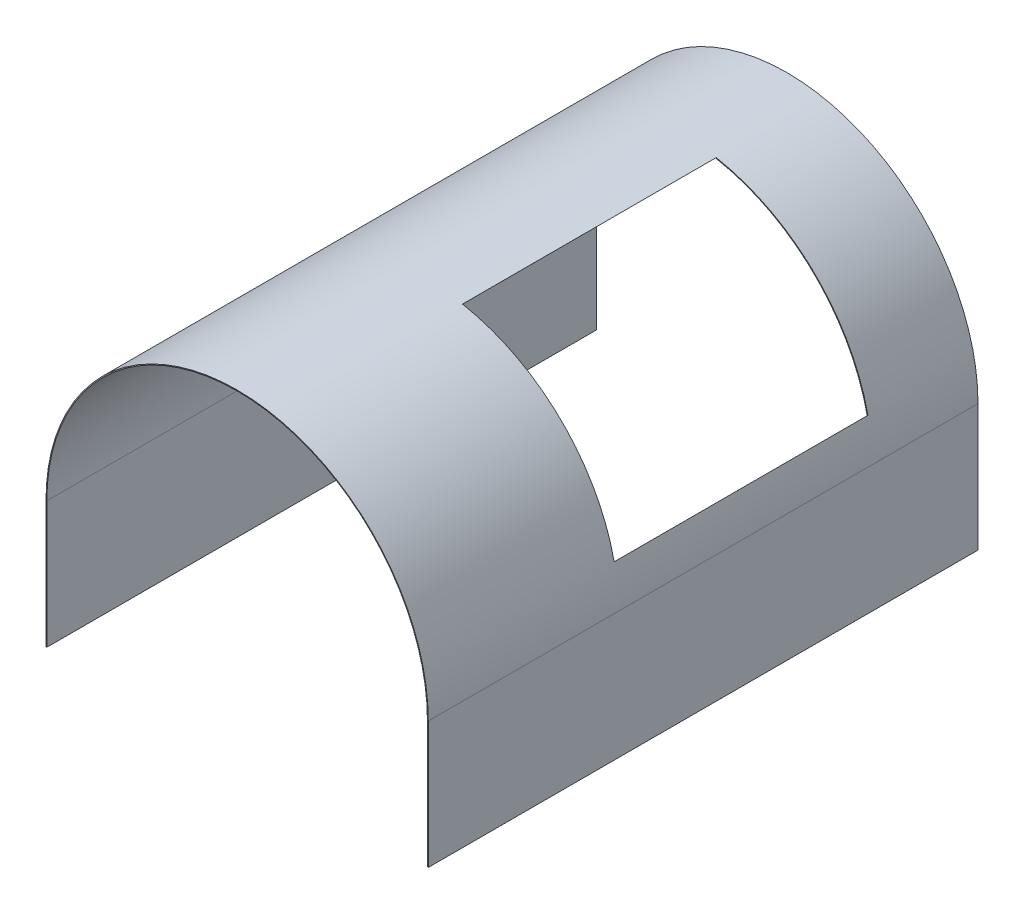
SolidWorks part; units mm, degrees
ref_plane "Front Plane" through (0, 0, 0) normal (0, 0, 1) x (1, 0, 0)
ref_plane "Top Plane" through (0, 0, 0) normal (0, 1, 0) x (1, 0, 0)
ref_plane "Right Plane" through (0, 0, 0) normal (1, 0, 0) x (0, 0, -1)
sketch "Sketch1" plane through (0, 0, 0) normal (0, 0, 1) x (1, 0, 0)
  line L0 (-228.6, -36.83) -> (-228.6, -189.23)
  line L1 (-228.6, -189.23) -> (230.632, -189.23)
  line L2 (-228.6, -189.23) -> (-228.6, 192.786) construction
  line L3 (-228.6, 192.786) -> (230.632, 192.786) construction
  line L4 (230.632, -189.23) -> (230.632, 192.786) construction
  line L5 (230.632, -36.83) -> (230.632, -189.23)
  circle A0 centre (0, 0) radius 127 construction
  arc A2 (230.632, -36.83) -> (-228.6, -36.83) centre (1.016, -36.83) ccw
  dimension "D1" = 254
  dimension "D4" = 189.23
  dimension "D5" = 228.6
  dimension "D2" = 459.232
  dimension "D3" = 382.016
extrude "Boss-Extrude1" add sketch "Sketch1" along normal blind 660.4
sketch "Sketch2" plane through (0, 0, 660.4) normal (0, 0, 1) x (1, 0, 0)
  line L0 (-228.6, -189.23) -> (230.632, -189.23) construction
  line L2 (-227.584, -36.83) -> (-227.584, -189.23)
  line L3 (-227.584, -189.23) -> (229.616, -189.23)
  line L4 (229.616, -36.83) -> (229.616, -189.23)
  line L5 (-187.6415, 88.9417) -> (229.616, -189.23) construction
  line L6 (-227.584, -189.23) -> (189.6735, 88.9417) construction
  arc A1 (229.616, -36.83) -> (-227.584, -36.83) centre (1.016, -36.83) ccw
  dimension "D2" = 457.2
extrude "Cut-Extrude1" cut sketch "Sketch2" against normal blind 660.4
ref_plane "Plane1" through (96.3898, 96.8182, 0) normal (0.7055, 0.7087, 0) x (0.7087, -0.7055, 0)
sketch "Sketch3" plane through (96.3898, 96.8182, 0) normal (0.7055, 0.7087, 0) x (0.7087, -0.7055, 0)
  line L0 (189.4276, -660.4) -> (189.4276, 0) construction
  line L1 (-102.6724, -127) -> (151.3276, -127)
  line L2 (-102.6724, -127) -> (-102.6724, -431.8)
  line L3 (-102.6724, -431.8) -> (151.3276, -431.8)
  line L4 (151.3276, -127) -> (151.3276, -431.8)
  line L5 (-102.6724, -127) -> (151.3276, -431.8) construction
  line L6 (-102.6724, -431.8) -> (151.3276, -127) construction
  line L7 (189.4276, 0) -> (-202.9111, 0) construction
  point P0 (24.3276, -279.4)
  dimension "D1" = 304.8
  dimension "D2" = 254
  dimension "D3" = 38.1
  dimension "D4" = 127
extrude "Cut-Extrude2" cut sketch "Sketch3" along normal blind 152.4
